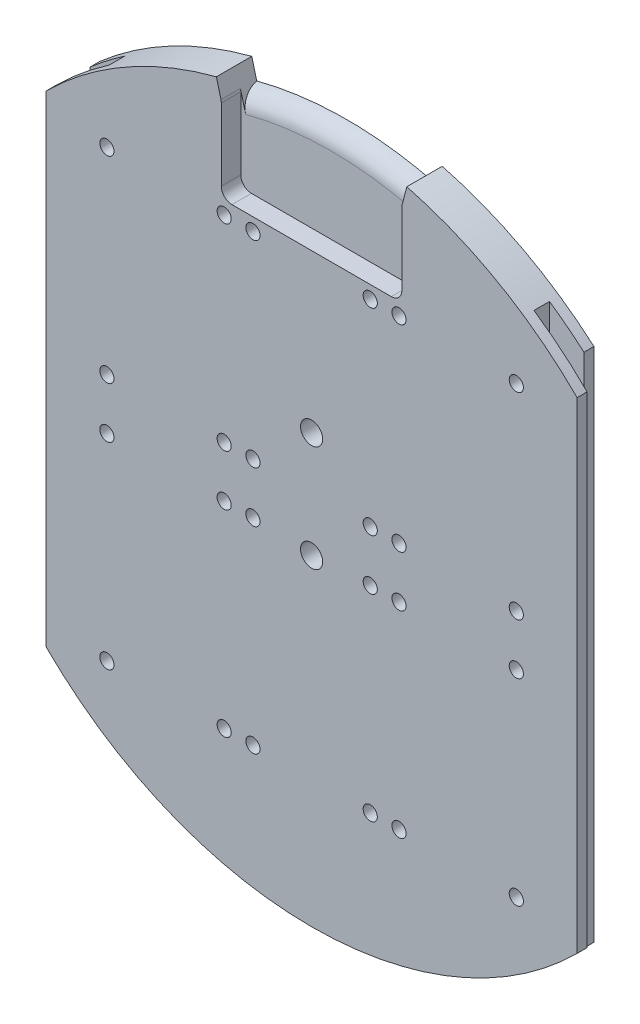
SolidWorks part; units mm, degrees
material "ABS"
ref_plane "Plano frontal" through (0, 0, 0) normal (0, 0, 1) x (1, 0, 0)
ref_plane "Plano superior" through (0, 0, 0) normal (0, 1, 0) x (1, 0, 0)
ref_plane "Plano direito" through (0, 0, 0) normal (1, 0, 0) x (0, 0, -1)
sketch "Esboço1" plane through (0, 0, 0) normal (0, 0, 1) x (1, 0, 0)
  line L0 (0, 0) -> (0, -108.75)
  line L1 (120, -108.75) -> (120, 0)
  line L2 (60, -11.4098) -> (60, -97.3402) construction
  line L3 (120, -54.375) -> (-37.4329, -54.375) construction
  line L8 (12.1875, -86.25) -> (107.8125, -22.5) construction
  line L9 (12.1875, -22.5) -> (107.8125, -86.25) construction
  arc A4 (0, 0) -> (120, 0) centre (60, -60.208) cw
  arc A5 (0, -108.75) -> (120, -108.75) centre (60, -48.542) ccw
  point P9 (60, -54.375)
  point P17 (60, 24.792)
  dimension "D1" = 108.75
  dimension "D5" = 85
  dimension "D2" = 63.75
  dimension "D3" = 95.625
extrude "Ressalto-extrusão1" add sketch "Esboço1" along normal blind 8
sketch "Esboço5" plane through (0, 0, 8) normal (0, 0, 1) x (1, 0, 0)
  line L0 (60, 24.792) -> (60, -133.542) construction
  line L1 (44.6956, -48.875) -> (75, -48.875) construction
  line L5 (44.6956, -79.875) -> (75, -79.875)
  line L6 (44.6956, -79.875) -> (44.6956, -17.875)
  line L7 (44.6956, -17.875) -> (75, -17.875)
  line L8 (75, -79.875) -> (75, -17.875)
  arc A0 (120, 0) -> (0, 0) centre (60, -60.208) ccw construction
  arc A1 (0, -108.75) -> (120, -108.75) centre (60, -48.542) ccw construction
  circle A2 centre (60, -60.875) radius 2.5
  circle A4 centre (60, -36.875) radius 2.5
  dimension "D1" = 5
  dimension "D2" = 12
  dimension "D4" = 30.3044
  dimension "D3" = 62
  dimension "D5" = 15
  dimension "D6" = 73.667
extrude "Corte-extrusão3" cut sketch "Esboço5" against normal blind 5 contours A4 | A2
sketch "Esboço7" plane through (0, 0, 0) normal (0, 0, -1) x (-1, 0, 0)
  line L0 (-60, 24.792) -> (-60, -133.542) construction
  line L1 (-120, -54.375) -> (0, -54.375) construction
  line L2 (-120, -108.75) -> (-120, 0) construction
  line L3 (0, 0) -> (0, -108.75) construction
  line L4 (-106.25, -26.375) -> (-73.25, -26.375) construction
  line L5 (-13.75, -26.375) -> (-46.75, -26.375) construction
  line L6 (-13.75, -82.375) -> (-46.75, -82.375) construction
  line L7 (-106.25, -82.375) -> (-73.25, -82.375) construction
  arc A0 (0, 0) -> (-120, 0) centre (-60, -60.208) ccw construction
  arc A1 (-120, -108.75) -> (0, -108.75) centre (-60, -48.542) ccw construction
  circle A2 centre (-73.25, -48.625) radius 1.6
  circle A3 centre (-79.75, -48.625) radius 1.6
  circle A4 centre (-106.25, -48.625) radius 1.6
  circle A5 centre (-73.25, -4.125) radius 1.6
  circle A6 centre (-106.25, -4.125) radius 1.6
  circle A7 centre (-79.75, -4.125) radius 1.6
  circle A8 centre (-40.25, -4.125) radius 1.6
  circle A9 centre (-13.75, -4.125) radius 1.6
  circle A10 centre (-46.75, -4.125) radius 1.6
  circle A11 centre (-13.75, -48.625) radius 1.6
  circle A12 centre (-40.25, -48.625) radius 1.6
  circle A13 centre (-46.75, -48.625) radius 1.6
  circle A14 centre (-46.75, -60.125) radius 1.6
  circle A15 centre (-40.25, -60.125) radius 1.6
  circle A16 centre (-13.75, -60.125) radius 1.6
  circle A17 centre (-46.75, -104.625) radius 1.6
  circle A18 centre (-13.75, -104.625) radius 1.6
  circle A19 centre (-40.25, -104.625) radius 1.6
  circle A20 centre (-79.75, -104.625) radius 1.6
  circle A21 centre (-106.25, -104.625) radius 1.6
  circle A22 centre (-73.25, -104.625) radius 1.6
  circle A23 centre (-106.25, -60.125) radius 1.6
  circle A24 centre (-79.75, -60.125) radius 1.6
  circle A25 centre (-73.25, -60.125) radius 1.6
  dimension "D1" = 3.2
  dimension "D2" = 3.2
  dimension "D3" = 3.2
  dimension "D4" = 5.75
  dimension "D5" = 13.25
  dimension "D6" = 6.5
  dimension "D7" = 26.5
  dimension "D8" = 22.25
extrude "Corte-extrusão4" cut sketch "Esboço7" against normal through all
sketch "Esboço9" plane through (0, 0, 8) normal (0, 0, 1) x (1, 0, 0)
  line L0 (39.6, 17.7677) -> (38.4864, 22.0244)
  line L1 (60, 24.792) -> (60, -133.542) construction
  line L2 (80.4, 17.7677) -> (81.5136, 22.0244)
  arc A0 (120, 0) -> (0, 0) centre (60, -60.208) ccw construction
  arc A1 (81.5136, 22.0244) -> (38.4864, 22.0244) centre (60, -60.208) ccw
  arc A2 (80.4, 17.7677) -> (39.6, 17.7677) centre (60, -60.208) ccw
  arc A3 (81.5136, 22.0244) -> (0, 0) centre (60, -60.208) ccw construction
  arc A4 (80.4, 17.7677) -> (3.1059, -3.1166) centre (60, -60.208) ccw construction
  arc A5 (0, -108.75) -> (120, -108.75) centre (60, -48.542) ccw construction
  dimension "D2" = 20.4
  dimension "D1" = 4.4
extrude "Corte-extrusão6" cut sketch "Esboço9" against normal through all
sketch "Esboço10" plane through (0, 0, 8) normal (0, 0, 1) x (1, 0, 0)
  line L0 (39.6, 17.7677) -> (39.6, -1.2323)
  line L1 (39.6, -1.2323) -> (80.4, -1.2323)
  line L2 (80.4, -1.2323) -> (80.4, 17.7677)
  arc A0 (80.4, 17.7677) -> (39.6, 17.7677) centre (60, -60.208) ccw construction
  arc A1 (80.4, 17.7677) -> (39.6, 17.7677) centre (60, -60.208) ccw
  dimension "D1" = 19
extrude "Corte-extrusão7" cut sketch "Esboço10" against normal blind 4.4 contours L2 A1 L0 L1
fillet "Filete1" radius 2.4 4 edges at (80.4, -1.2323, 5.8) (39.6, -1.2323, 5.8) (80.4, 17.7677, 5.8) (39.6, 17.7677, 5.8)
fillet "Filete2" radius 4.4 1 edges at (60, 20.392, 3.6)
sketch "Esboço11" plane through (0, 0, 0) normal (-1, 0, 0) x (0, 0, 1)
  line L1 (2.25, -128.75) -> (5.75, -128.75)
  line L2 (2.25, -128.75) -> (2.25, 21.25)
  line L3 (2.25, 21.25) -> (5.75, 21.25)
  line L4 (5.75, -128.75) -> (5.75, 21.25)
  line L5 (0, 0) -> (0, -108.75) construction
  line L6 (8, -108.75) -> (0, -108.75) construction
  dimension "D1" = 3.5
  dimension "D2" = 150
  dimension "D3" = 2.25
  dimension "D4" = 20
extrude "Corte-extrusão8" cut sketch "Esboço11" against normal blind 12
sketch "Esboço12" plane through (120, 0, 0) normal (1, 0, 0) x (0, 0, -1)
  line L1 (-2.25, -128.75) -> (-5.75, -128.75)
  line L2 (-2.25, -128.75) -> (-2.25, 21.25)
  line L3 (-2.25, 21.25) -> (-5.75, 21.25)
  line L4 (-5.75, -128.75) -> (-5.75, 21.25)
  line L5 (-8, -108.75) -> (-8, 0) construction
  line L6 (-8, -108.75) -> (0, -108.75) construction
  dimension "D1" = 3.5
  dimension "D2" = 150
  dimension "D3" = 2.25
  dimension "D4" = 20
extrude "Corte-extrusão9" cut sketch "Esboço12" against normal blind 12
sketch "Esboço13" plane through (0, 0, 0) normal (0, 0, -1) x (-1, 0, 0)
  line L0 (-60, 20.392) -> (-60, -133.542) construction
  line L1 (0, -54.375) -> (-120.2, -54.375) construction
  line L2 (-120.2, 22.6494) -> (-115.8, 22.6494)
  line L3 (-120.2, 22.6494) -> (-120.2, -134.167)
  line L4 (-120.2, -134.167) -> (-115.8, -134.167)
  line L5 (-115.8, 22.6494) -> (-115.8, -134.167)
  line L6 (0, 0) -> (0, -108.75) construction
  line L7 (-4.2, 22.6494) -> (-4.2, -134.167)
  line L8 (0.2, -134.167) -> (-4.2, -134.167)
  line L9 (0.2, 22.6494) -> (0.2, -134.167)
  line L10 (0.2, 22.6494) -> (-4.2, 22.6494)
  arc A0 (-39.6, 17.7677) -> (-80.4, 17.7677) centre (-60, -60.208) ccw construction
  arc A1 (-120, -108.75) -> (0, -108.75) centre (-60, -48.542) ccw construction
  dimension "D1" = 4.4
  dimension "D2" = 156.8164
  dimension "D3" = 55.8
  dimension "D4" = 79.792
extrude "Corte-extrusão10" cut sketch "Esboço13" against normal blind 5.75
